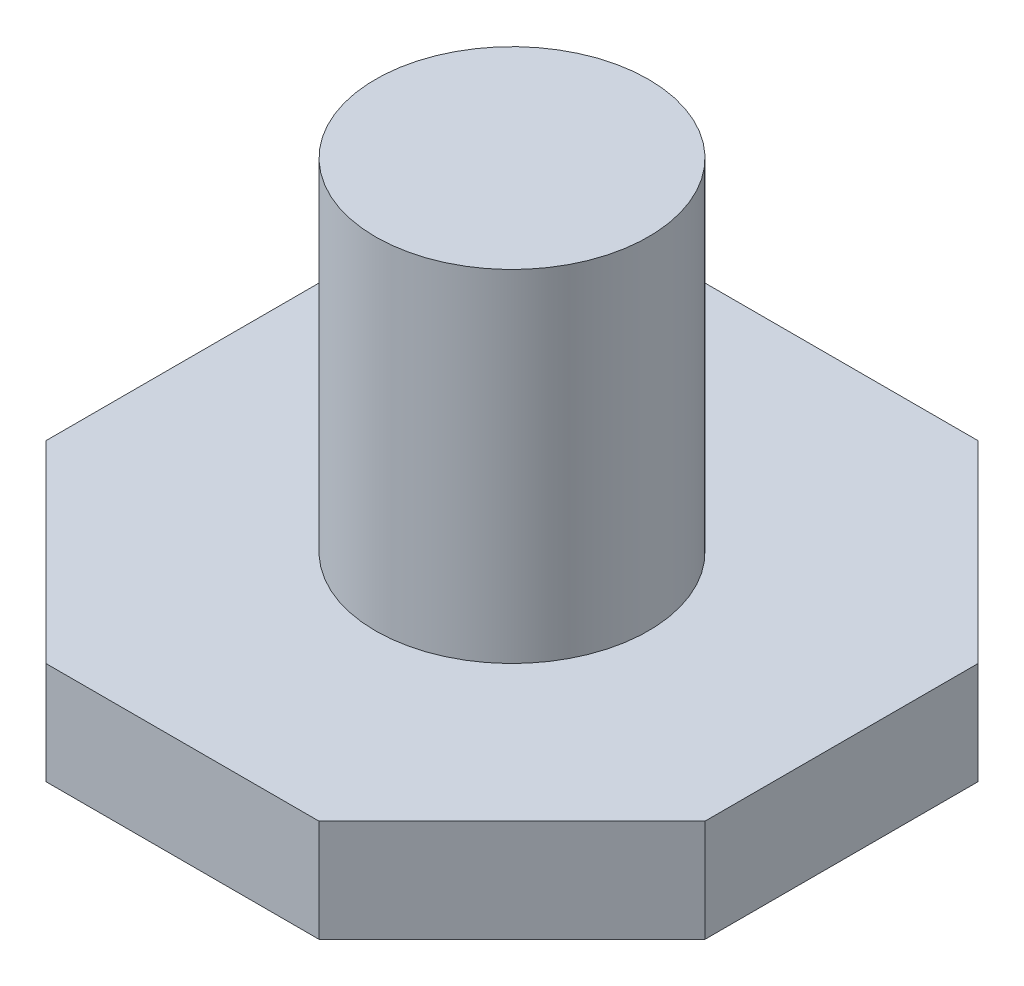
SolidWorks part; units mm, degrees
ref_plane "前视基准面" through (0, 0, 0) normal (0, 0, 1) x (1, 0, 0)
ref_plane "上视基准面" through (0, 0, 0) normal (0, 1, 0) x (1, 0, 0)
ref_plane "右视基准面" through (0, 0, 0) normal (1, 0, 0) x (0, 0, -1)
other "Configuration Table"
sketch "草图1" plane through (0, 0, 0) normal (0, 1, 0) x (1, 0, 0)
  line L0 (-10.8126, 0) -> (9.6996, 0) construction
  line L1 (2, 4.8284) -> (-2, 4.8284)
  line L11 (-2, 4.8284) -> (-4.8284, 2)
  line L12 (-4.8284, 2) -> (-4.8284, -2)
  line L13 (-4.8284, -2) -> (-2, -4.8284)
  line L14 (-2, -4.8284) -> (2, -4.8284)
  line L15 (2, -4.8284) -> (4.8284, -2)
  line L16 (4.8284, -2) -> (4.8284, 2)
  line L17 (4.8284, 2) -> (2, 4.8284)
  line L18 (0, 8.0936) -> (0, -9.5565) construction
  circle A0 centre (0, 0) radius 2
  dimension "D1" = 4
  dimension "D2" = 4
extrude "凸台-拉伸4" add sketch "草图1" against normal blind 1.5 contours L16 L17 L1 L11 L12 L13 L14 L15 A0 | A0 region at (3.3176, 0, -3.3176) region at (0, 0, 0)
extrude "凸台-拉伸5" add sketch "草图1<5>" along normal blind 5 contours A0 region at (0, 0, 0)
sketch "草图1<5>" plane through (0, 0, 0) normal (0, 1, 0) x (1, 0, 0) same geometry as "草图1"
